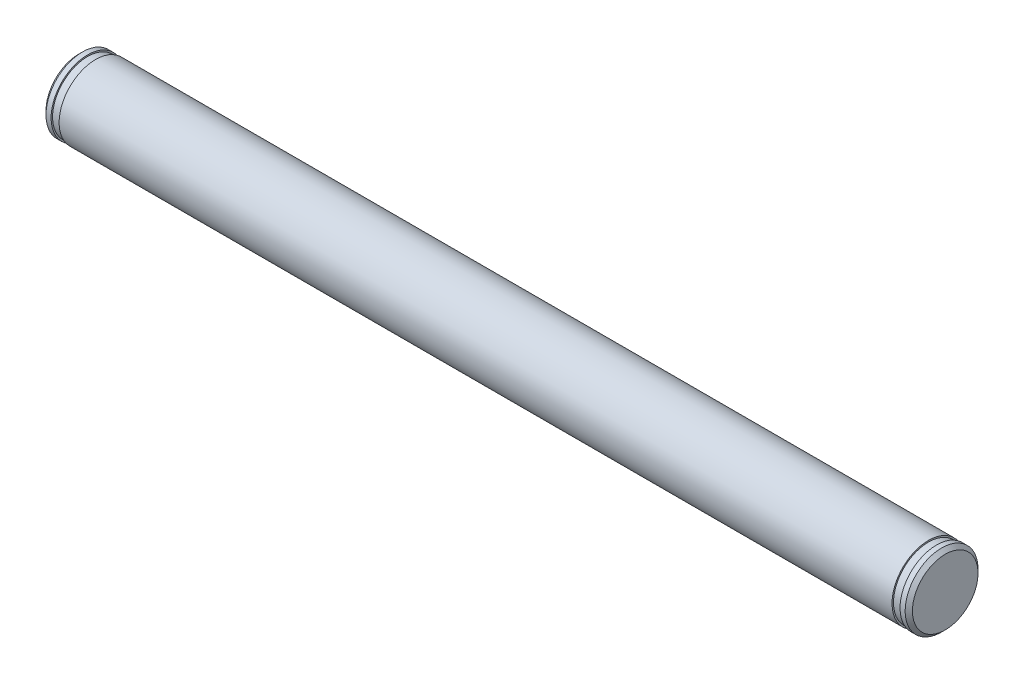
SolidWorks part; units mm, degrees
ref_plane "前视基准面" through (0, 0, 0) normal (0, 0, 1) x (1, 0, 0)
ref_plane "上视基准面" through (0, 0, 0) normal (0, 1, 0) x (1, 0, 0)
ref_plane "右视基准面" through (0, 0, 0) normal (1, 0, 0) x (0, 0, -1)
other "Configuration Table"
sketch "草图1" plane through (0, 0, 0) normal (0, 0, 1) x (1, 0, 0)
  line L0 (-59.45, 0) -> (59.45, 0) construction
  line L1 (59.45, 0) -> (59.45, 5)
  line L2 (59.45, 5) -> (58.25, 5)
  line L3 (58.25, 5) -> (58.25, 4.8)
  line L4 (58.25, 4.8) -> (57.15, 4.8)
  line L5 (57.15, 4.8) -> (57.15, 5)
  line L6 (57.15, 5) -> (-57.15, 5)
  line L7 (0, 5) -> (0, 0) construction
  line L8 (57.25, 4.8) -> (57.25, 0) construction
  line L9 (-59.45, 0) -> (-59.45, 5)
  line L10 (-57.25, 4.8) -> (-57.25, 0) construction
  line L11 (-57.15, 4.8) -> (-57.15, 5)
  line L12 (-58.25, 4.8) -> (-57.15, 4.8)
  line L13 (-58.25, 5) -> (-58.25, 4.8)
  line L14 (-59.45, 5) -> (-58.25, 5)
  line L15 (59.45, 0) -> (-59.45, 0)
  dimension "D1" = 1.1
  dimension "D2" = 1
  dimension "D3" = 10
  dimension "D4" = 9.6
  dimension "D5" = 1.2
  dimension "D6" = 114.5
revolve "旋转1" add sketch "草图1" angle 360 about L15
chamfer "倒角1" distance 0.5 angle 45 2 edges at (59.45, 5, 0) (-59.45, 5, 0)
ref_plane "基准面1" through (57.25, 0, 0) normal (1, 0, 0) x (0, 0, -1)
ref_plane "基准面2" through (-57.25, 0, 0) normal (-1, 0, 0) x (0, 0, 1)
ref_axis "基准轴1" through (-57.15, 0, 0) along (1, 0, 0)
